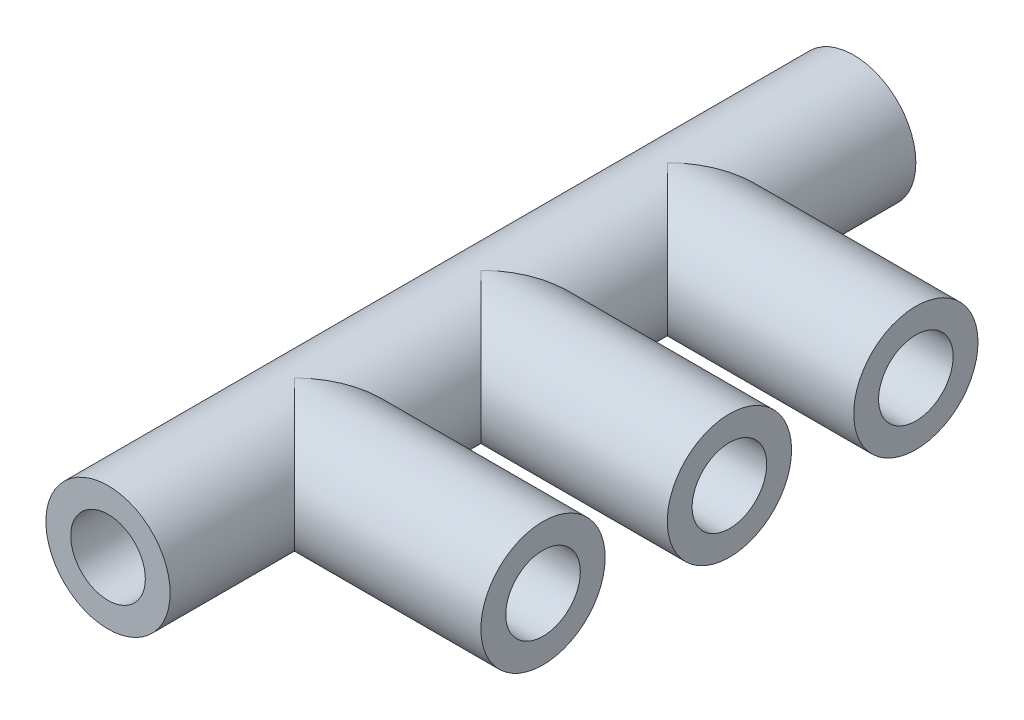
SolidWorks part; units mm, degrees
ref_plane "Plan de face" through (0, 0, 0) normal (0, 0, 1) x (1, 0, 0)
ref_plane "Plan de dessus" through (0, 0, 0) normal (0, 1, 0) x (1, 0, 0)
ref_plane "Plan de droite" through (0, 0, 0) normal (1, 0, 0) x (0, 0, -1)
sketch "Esquisse1" plane through (0, 0, 0) normal (0, 0, 1) x (1, 0, 0)
  circle A0 centre (0, 0) radius 5
  dimension "D1" = 10
extrude "Boss.-Extru.1" add sketch "Esquisse1" along normal blind 60
sketch "Esquisse2" plane through (0, 0, 0) normal (1, 0, 0) x (0, 0, -1)
  line L0 (0, 0) -> (-64.2165, 0) construction
  line L1 (-60, 5) -> (-60, -5) construction
  circle A0 centre (-15, 0) radius 5
  circle A1 centre (-30, 0) radius 5
  circle A2 centre (-45, 0) radius 5
  point P9 (0, 0)
  point P10 (0, 0)
  dimension "D1" = 10
  dimension "D2" = 10
  dimension "D3" = 10
  dimension "D4" = 15
  dimension "D5" = 30
  dimension "D6" = 15
extrude "Boss.-Extru.2" add sketch "Esquisse2" along normal blind 20
shell "Coque1" thickness 2 removed face at (5, 0, 60) removed face at (20, 0, 40) removed face at (20, 0, 25) removed face at (20, 0, 10) removed face at (5, 0, 0)
